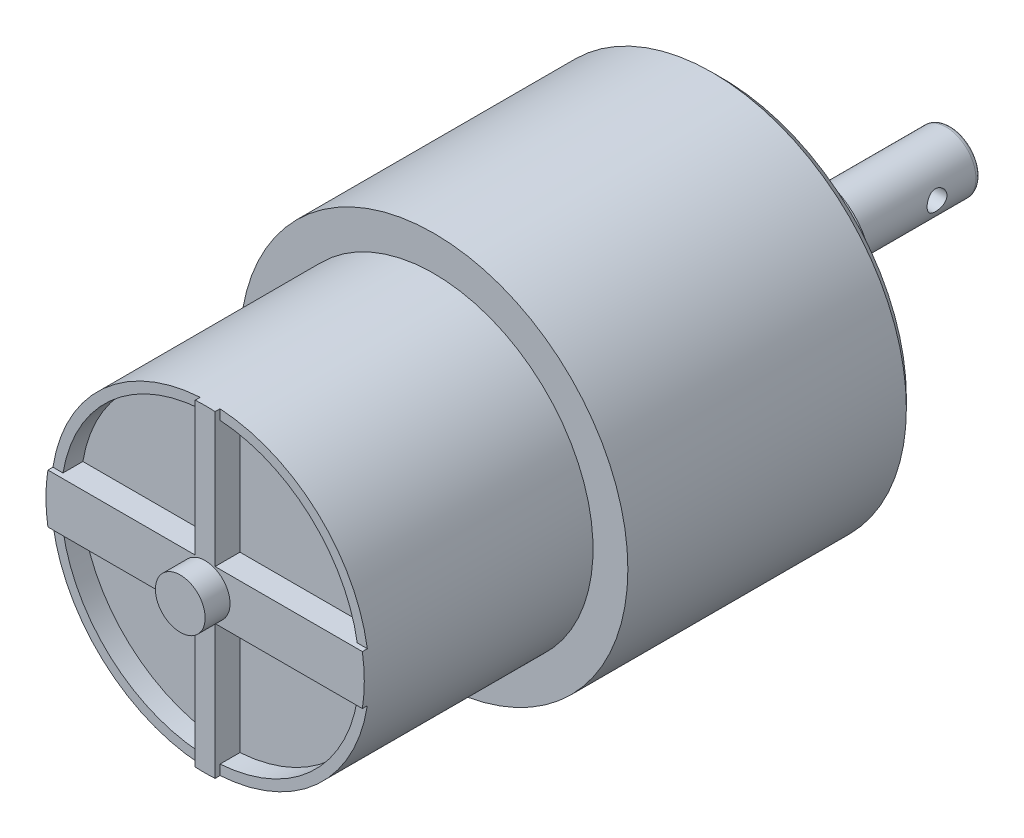
SolidWorks part; units mm, degrees
ref_plane "Front Plane" through (0, 0, 0) normal (0, 0, 1) x (1, 0, 0)
ref_plane "Top Plane" through (0, 0, 0) normal (0, 1, 0) x (1, 0, 0)
ref_plane "Right Plane" through (0, 0, 0) normal (1, 0, 0) x (0, 0, -1)
sketch "Sketch1" plane through (0, 0, 0) normal (0, 0, 1) x (1, 0, 0)
  circle A0 centre (0, 0) radius 16
  dimension "D1" = 32
extrude "Boss-Extrude1" add sketch "Sketch1" along normal blind 23
sketch "Sketch2" plane through (0, 0, 0) normal (0, 0, -1) x (-1, 0, 0)
  circle A0 centre (0, 0) radius 19.5
  dimension "D1" = 39
extrude "Boss-Extrude2" add sketch "Sketch2" along normal blind 29
sketch "Sketch3" plane through (0, 0, -29) normal (0, 0, -1) x (-1, 0, 0)
  circle A0 centre (0, 0) radius 6
  dimension "D1" = 12
extrude "Boss-Extrude4" add sketch "Sketch3" along normal blind 9
sketch "Sketch4" plane through (0, 0, -38) normal (0, 0, -1) x (-1, 0, 0)
  circle A0 centre (0, 0) radius 3
  dimension "D1" = 6
extrude "Boss-Extrude5" add sketch "Sketch4" along normal blind 22
sketch "Sketch5" plane through (0, 0, 0) normal (1, 0, 0) x (0, 0, -1)
  line L0 (60, -3) -> (60, 3) construction
  circle A0 centre (52, 0) radius 1.5
  dimension "D1" = 3
  dimension "D2" = 8
extrude "Cut-Extrude2" cut sketch "Sketch5" against normal blind 22 and the other way blind 22
sketch "Sketch6" plane through (0, 0, 23) normal (0, 0, 1) x (1, 0, 0)
  line L0 (0.9981, -2.4815) -> (0.9981, -15.9688)
  line L2 (-0.9981, 15.9688) -> (-0.9981, 2.4815)
  line L4 (0.9981, 15.9688) -> (0.9981, 2.4815)
  line L5 (0.9981, 2.4815) -> (15.8064, 2.4815)
  line L6 (0.9981, -2.4815) -> (15.8064, -2.4815)
  line L7 (-15.8064, -2.4815) -> (-0.9981, -2.4815)
  line L9 (-15.8064, 2.4815) -> (-0.9981, 2.4815)
  line L13 (-0.9981, -2.4815) -> (-0.9981, -15.9688)
  circle A0 centre (0, 0) radius 16 construction
  circle A1 centre (0, 0) radius 16 construction
  arc A2 (15.8064, 2.4815) -> (0.9981, 15.9688) centre (0, 0) ccw
  arc A3 (-15.8064, -2.4815) -> (-0.9981, -15.9688) centre (0, 0) ccw
  arc A4 (-0.9981, 15.9688) -> (-15.8064, 2.4815) centre (0, 0) ccw
  arc A6 (0.9981, -15.9688) -> (15.8064, -2.4815) centre (0, 0) ccw
  point P0 (0, 0)
  point P8 (0, 0)
extrude "Cut-Extrude4" cut sketch "Sketch6" against normal blind 2.5
sketch "Sketch7" plane through (0, 0, 23) normal (0, 0, 1) x (1, 0, 0)
  circle A0 centre (0, 0) radius 2.5
  dimension "D1" = 5
extrude "Boss-Extrude6" add sketch "Sketch7" along normal blind 2.5
sketch "Sketch8" plane through (0, 0, 20.5) normal (0, 0, 1) x (1, 0, 0)
  line L0 (-15.8064, 2.4815) -> (-14.7933, 2.4815)
  line L1 (-15.8064, 2.4815) -> (-0.9981, 2.4815) construction
  line L2 (-0.9981, 15.9688) -> (-0.9981, 14.9668)
  line L3 (0.9981, 15.9688) -> (0.9981, 14.9668)
  line L4 (14.7933, 2.4815) -> (15.8064, 2.4815)
  line L5 (15.8064, -2.4815) -> (14.7933, -2.4815)
  line L6 (0.9981, -15.9688) -> (0.9981, -14.9668)
  line L7 (0.9981, -2.4815) -> (0.9981, -15.9688) construction
  line L8 (-0.9981, -15.9688) -> (-0.9981, -14.9668)
  line L9 (-14.7933, -2.4815) -> (-15.8064, -2.4815)
  arc A0 (-15.8064, -2.4815) -> (-0.9981, -15.9688) centre (0, 0) ccw
  arc A1 (-14.7933, -2.4815) -> (-0.9981, -14.9668) centre (0, 0) ccw
  arc A2 (-0.9981, 14.9668) -> (-14.7933, 2.4815) centre (0, 0) ccw
  arc A3 (-0.9981, 15.9688) -> (-15.8064, 2.4815) centre (0, 0) ccw
  arc A4 (14.7933, 2.4815) -> (0.9981, 14.9668) centre (0, 0) ccw
  arc A5 (15.8064, 2.4815) -> (0.9981, 15.9688) centre (0, 0) ccw
  arc A6 (0.9981, -15.9688) -> (15.8064, -2.4815) centre (0, 0) ccw
  arc A7 (0.9981, -14.9668) -> (14.7933, -2.4815) centre (0, 0) ccw
  dimension "D1" = 30
extrude "Boss-Extrude7" add sketch "Sketch8" along normal blind 2
chamfer "Chamfer1" distance 1 angle 45 1 edges at (-19.5, 0, -29)
fillet "Fillet1" radius 1 1 edges at (-3, 0, -60)
sketch "Sketch9" plane through (0, 0, -60) normal (0, 0, -1) x (-1, 0, 0)
  circle A0 centre (0, 0) radius 3
extrude "Boss-Extrude8" add sketch "Sketch9" against normal blind 22
sketch "Sketch10" plane through (0, 0, -60) normal (0, 0, -1) x (-1, 0, 0)
  circle A0 centre (0, 0) radius 3
extrude "Cut-Extrude6" cut sketch "Sketch10" against normal blind 8
fillet "Fillet2" radius 0.5 1 edges at (-3, 0, -52)
sketch "Sketch11" plane through (0, 0, 0) normal (1, 0, 0) x (0, 0, -1)
  circle A0 centre (47.5841, 0) radius 1
  dimension "D1" = 2
extrude "Cut-Extrude7" cut sketch "Sketch11" against normal through all and the other way through all
